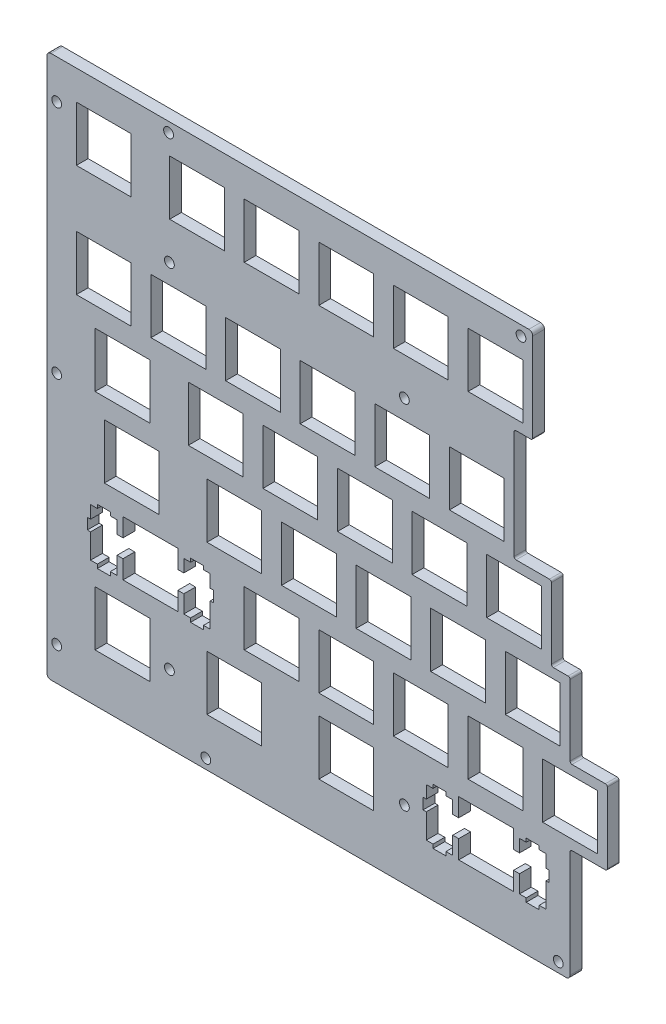
SolidWorks part; units mm, degrees
ref_plane "前视基准面" through (0, 0, 0) normal (0, 0, 1) x (1, 0, 0)
ref_plane "上视基准面" through (0, 0, 0) normal (0, 1, 0) x (1, 0, 0)
ref_plane "右视基准面" through (0, 0, 0) normal (1, 0, 0) x (0, 0, -1)
other "Configuration Table"
sketch "Model" plane through (0, 0, 0) normal (0, 0, 1) x (1, 0, 0)
  line L0 (0.0951, 124.083) -> (119.158, 124.083)
  line L1 (138.208, 124.083) -> (138.208, 0.2577) construction
  line L2 (128.683, 0.2577) -> (0.0951, 0.2577)
  line L3 (0.0951, 0.2577) -> (0.0951, 124.083)
  line L4 (100.251, 16.7831) -> (100.251, 12.0826)
  line L5 (100.251, 12.0826) -> (98.7256, 12.0826)
  line L6 (98.7256, 12.0826) -> (98.7256, 15.3128)
  line L7 (98.7256, 15.3128) -> (97.0001, 15.3128)
  line L8 (97.0001, 15.3128) -> (97.0001, 16.2333)
  line L9 (97.0001, 16.2333) -> (93.701, 16.2333)
  line L10 (93.701, 16.2333) -> (93.701, 15.3128)
  line L11 (93.701, 15.3128) -> (91.9759, 15.3128)
  line L12 (91.9759, 15.3128) -> (91.9759, 12.0826)
  line L13 (91.9759, 12.0826) -> (91.1504, 12.0826)
  line L14 (91.1504, 12.0826) -> (91.1504, 9.2838)
  line L15 (91.1504, 9.2838) -> (91.9759, 9.2838)
  line L16 (91.9759, 9.2838) -> (91.9759, 3.0138)
  line L17 (91.9759, 3.0138) -> (93.701, 3.0138)
  line L18 (93.701, 3.0138) -> (93.701, 2.0326)
  line L19 (93.701, 2.0326) -> (97.0001, 2.0326)
  line L20 (97.0001, 2.0326) -> (97.0001, 3.0138)
  line L21 (97.0001, 3.0138) -> (98.7256, 3.0138)
  line L22 (98.7256, 3.0138) -> (98.7256, 7.4827)
  line L23 (98.7256, 7.4827) -> (100.251, 7.4827)
  line L24 (100.251, 7.4827) -> (100.251, 2.7836)
  line L25 (100.251, 2.7836) -> (114.25, 2.7836)
  line L26 (114.25, 2.7836) -> (114.25, 7.4827)
  line L27 (114.25, 7.4827) -> (115.776, 7.4827)
  line L28 (115.776, 7.4827) -> (115.776, 3.0138)
  line L29 (115.776, 3.0138) -> (117.5, 3.0138)
  line L30 (117.5, 3.0138) -> (117.5, 2.0326)
  line L31 (117.5, 2.0326) -> (120.8, 2.0326)
  line L32 (120.8, 2.0326) -> (120.8, 3.0138)
  line L33 (120.8, 3.0138) -> (122.525, 3.0138)
  line L34 (122.525, 3.0138) -> (122.525, 9.2838)
  line L35 (122.525, 9.2838) -> (123.351, 9.2838)
  line L36 (123.351, 9.2838) -> (123.351, 12.0826)
  line L37 (123.351, 12.0826) -> (122.525, 12.0826)
  line L38 (122.525, 12.0826) -> (122.525, 15.3128)
  line L39 (122.525, 15.3128) -> (120.8, 15.3128)
  line L40 (120.8, 15.3128) -> (120.8, 16.2333)
  line L41 (120.8, 16.2333) -> (117.5, 16.2333)
  line L42 (117.5, 16.2333) -> (117.5, 15.3128)
  line L43 (117.5, 15.3128) -> (115.776, 15.3128)
  line L44 (115.776, 15.3128) -> (115.776, 12.0826)
  line L45 (115.776, 12.0826) -> (114.25, 12.0826)
  line L46 (114.25, 12.0826) -> (114.25, 16.7831)
  line L47 (114.25, 16.7831) -> (100.251, 16.7831)
  line L48 (7.3822, 16.7831) -> (21.3817, 16.7831)
  line L49 (21.3817, 16.7831) -> (21.3817, 2.7836)
  line L50 (21.3817, 2.7836) -> (7.3822, 2.7836)
  line L51 (7.3822, 2.7836) -> (7.3822, 16.7831)
  line L52 (35.9572, 16.7831) -> (49.9565, 16.7831)
  line L53 (49.9565, 16.7831) -> (49.9565, 2.7836)
  line L54 (49.9565, 2.7836) -> (35.9572, 2.7836)
  line L55 (35.9572, 2.7836) -> (35.9572, 16.7831)
  line L56 (64.5322, 16.7831) -> (78.5315, 16.7831)
  line L57 (78.5315, 16.7831) -> (78.5315, 2.7836)
  line L58 (78.5315, 2.7836) -> (64.5322, 2.7836)
  line L59 (64.5322, 2.7836) -> (64.5322, 16.7831)
  line L60 (14.5259, 35.833) -> (14.5259, 31.1326)
  line L61 (14.5259, 31.1326) -> (13.0004, 31.1326)
  line L62 (13.0004, 31.1326) -> (13.0004, 34.3628)
  line L63 (13.0004, 34.3628) -> (11.2751, 34.3628)
  line L64 (11.2751, 34.3628) -> (11.2751, 35.2834)
  line L65 (11.2751, 35.2834) -> (7.9761, 35.2834)
  line L66 (7.9761, 35.2834) -> (7.9761, 34.3628)
  line L67 (7.9761, 34.3628) -> (6.2508, 34.3628)
  line L68 (6.2508, 34.3628) -> (6.2508, 31.1326)
  line L69 (6.2508, 31.1326) -> (5.4253, 31.1326)
  line L70 (5.4253, 31.1326) -> (5.4253, 28.3338)
  line L71 (5.4253, 28.3338) -> (6.2508, 28.3338)
  line L72 (6.2508, 28.3338) -> (6.2508, 22.0638)
  line L73 (6.2508, 22.0638) -> (7.9761, 22.0638)
  line L74 (7.9761, 22.0638) -> (7.9761, 21.0826)
  line L75 (7.9761, 21.0826) -> (11.2751, 21.0826)
  line L76 (11.2751, 21.0826) -> (11.2751, 22.0638)
  line L77 (11.2751, 22.0638) -> (13.0004, 22.0638)
  line L78 (13.0004, 22.0638) -> (13.0004, 26.5327)
  line L79 (13.0004, 26.5327) -> (14.5259, 26.5327)
  line L80 (14.5259, 26.5327) -> (14.5259, 21.8336)
  line L81 (14.5259, 21.8336) -> (28.5254, 21.8336)
  line L82 (28.5254, 21.8336) -> (28.5254, 26.5327)
  line L83 (28.5254, 26.5327) -> (30.0509, 26.5327)
  line L84 (30.0509, 26.5327) -> (30.0509, 22.0638)
  line L85 (30.0509, 22.0638) -> (31.7748, 22.0638)
  line L86 (31.7748, 22.0638) -> (31.7748, 21.0826)
  line L87 (31.7748, 21.0826) -> (35.0752, 21.0826)
  line L88 (35.0752, 21.0826) -> (35.0752, 22.0638)
  line L89 (35.0752, 22.0638) -> (36.8004, 22.0638)
  line L90 (36.8004, 22.0638) -> (36.8004, 28.3338)
  line L91 (36.8004, 28.3338) -> (37.6259, 28.3338)
  line L92 (37.6259, 28.3338) -> (37.6259, 31.1326)
  line L93 (37.6259, 31.1326) -> (36.8004, 31.1326)
  line L94 (36.8004, 31.1326) -> (36.8004, 34.3628)
  line L95 (36.8004, 34.3628) -> (35.0752, 34.3628)
  line L96 (35.0752, 34.3628) -> (35.0752, 35.2834)
  line L97 (35.0752, 35.2834) -> (31.7748, 35.2834)
  line L98 (31.7748, 35.2834) -> (31.7748, 34.3628)
  line L99 (31.7748, 34.3628) -> (30.0509, 34.3628)
  line L100 (30.0509, 34.3628) -> (30.0509, 31.1326)
  line L101 (30.0509, 31.1326) -> (28.5254, 31.1326)
  line L102 (28.5254, 31.1326) -> (28.5254, 35.833)
  line L103 (28.5254, 35.833) -> (14.5259, 35.833)
  line L104 (45.4822, 35.833) -> (59.4815, 35.833)
  line L105 (59.4815, 35.833) -> (59.4815, 21.8336)
  line L106 (59.4815, 21.8336) -> (45.4822, 21.8336)
  line L107 (45.4822, 21.8336) -> (45.4822, 35.833)
  line L108 (64.5322, 35.833) -> (78.5315, 35.833)
  line L109 (78.5315, 35.833) -> (78.5315, 21.8336)
  line L110 (78.5315, 21.8336) -> (64.5322, 21.8336)
  line L111 (64.5322, 21.8336) -> (64.5322, 35.833)
  line L112 (83.5822, 35.833) -> (97.5815, 35.833)
  line L113 (97.5815, 35.833) -> (97.5815, 21.8336)
  line L114 (97.5815, 21.8336) -> (83.5822, 21.8336)
  line L115 (83.5822, 21.8336) -> (83.5822, 35.833)
  line L116 (102.632, 35.833) -> (116.632, 35.833)
  line L117 (116.632, 35.833) -> (116.632, 21.8336)
  line L118 (116.632, 21.8336) -> (102.632, 21.8336)
  line L119 (102.632, 21.8336) -> (102.632, 35.833)
  line L120 (121.682, 35.833) -> (135.682, 35.833)
  line L121 (135.682, 35.833) -> (135.682, 21.8336)
  line L122 (135.682, 21.8336) -> (121.682, 21.8336)
  line L123 (121.682, 21.8336) -> (121.682, 35.833)
  line L124 (9.762, 54.8831) -> (23.7629, 54.8831)
  line L125 (23.7629, 54.8831) -> (23.7629, 40.8838)
  line L126 (23.7629, 40.8838) -> (9.762, 40.8838)
  line L127 (9.762, 40.8838) -> (9.762, 54.8831)
  line L128 (35.9572, 54.8831) -> (49.9565, 54.8831)
  line L129 (49.9565, 54.8831) -> (49.9565, 40.8838)
  line L130 (49.9565, 40.8838) -> (35.9572, 40.8838)
  line L131 (35.9572, 40.8838) -> (35.9572, 54.8831)
  line L132 (55.0072, 54.8831) -> (69.0065, 54.8831)
  line L133 (69.0065, 54.8831) -> (69.0065, 40.8838)
  line L134 (69.0065, 40.8838) -> (55.0072, 40.8838)
  line L135 (55.0072, 40.8838) -> (55.0072, 54.8831)
  line L136 (74.0572, 54.8831) -> (88.0565, 54.8831)
  line L137 (88.0565, 54.8831) -> (88.0565, 40.8838)
  line L138 (88.0565, 40.8838) -> (74.0572, 40.8838)
  line L139 (74.0572, 40.8838) -> (74.0572, 54.8831)
  line L140 (93.1072, 54.8831) -> (107.107, 54.8831)
  line L141 (107.107, 54.8831) -> (107.107, 40.8838)
  line L142 (107.107, 40.8838) -> (93.1072, 40.8838)
  line L143 (93.1072, 40.8838) -> (93.1072, 54.8831)
  line L144 (112.157, 54.8831) -> (126.157, 54.8831)
  line L145 (126.157, 54.8831) -> (126.157, 40.8838)
  line L146 (126.157, 40.8838) -> (112.157, 40.8838)
  line L147 (112.157, 40.8838) -> (112.157, 54.8831)
  line L148 (7.3822, 73.9331) -> (21.3817, 73.9331)
  line L149 (21.3817, 73.9331) -> (21.3817, 59.9338)
  line L150 (21.3817, 59.9338) -> (7.3822, 59.9338)
  line L151 (7.3822, 59.9338) -> (7.3822, 73.9331)
  line L152 (31.1947, 73.9331) -> (45.194, 73.9331)
  line L153 (45.194, 73.9331) -> (45.194, 59.9338)
  line L154 (45.194, 59.9338) -> (31.1947, 59.9338)
  line L155 (31.1947, 59.9338) -> (31.1947, 73.9331)
  line L156 (50.2447, 73.9331) -> (64.244, 73.9331)
  line L157 (64.244, 73.9331) -> (64.244, 59.9338)
  line L158 (64.244, 59.9338) -> (50.2447, 59.9338)
  line L159 (50.2447, 59.9338) -> (50.2447, 73.9331)
  line L160 (69.2947, 73.9331) -> (83.294, 73.9331)
  line L161 (83.294, 73.9331) -> (83.294, 59.9338)
  line L162 (83.294, 59.9338) -> (69.2947, 59.9338)
  line L163 (69.2947, 59.9338) -> (69.2947, 73.9331)
  line L164 (88.3447, 73.9331) -> (102.344, 73.9331)
  line L165 (102.344, 73.9331) -> (102.344, 59.9338)
  line L166 (102.344, 59.9338) -> (88.3447, 59.9338)
  line L167 (88.3447, 59.9338) -> (88.3447, 73.9331)
  line L168 (107.395, 73.9331) -> (121.394, 73.9331)
  line L169 (121.394, 73.9331) -> (121.394, 59.9338)
  line L170 (121.394, 59.9338) -> (107.395, 59.9338)
  line L171 (107.395, 59.9338) -> (107.395, 73.9331)
  line L172 (2.6197, 92.9831) -> (16.6192, 92.9831)
  line L173 (16.6192, 92.9831) -> (16.6192, 78.9838)
  line L174 (16.6192, 78.9838) -> (2.6197, 78.9838)
  line L175 (2.6197, 78.9838) -> (2.6197, 92.9831)
  line L176 (21.6697, 92.9831) -> (35.669, 92.9831)
  line L177 (35.669, 92.9831) -> (35.669, 78.9838)
  line L178 (35.669, 78.9838) -> (21.6697, 78.9838)
  line L179 (21.6697, 78.9838) -> (21.6697, 92.9831)
  line L180 (40.7197, 92.9831) -> (54.719, 92.9831)
  line L181 (54.719, 92.9831) -> (54.719, 78.9838)
  line L182 (54.719, 78.9838) -> (40.7197, 78.9838)
  line L183 (40.7197, 78.9838) -> (40.7197, 92.9831)
  line L184 (59.7697, 92.9831) -> (73.769, 92.9831)
  line L185 (73.769, 92.9831) -> (73.769, 78.9838)
  line L186 (73.769, 78.9838) -> (59.7697, 78.9838)
  line L187 (59.7697, 78.9838) -> (59.7697, 92.9831)
  line L188 (78.8197, 92.9831) -> (92.819, 92.9831)
  line L189 (92.819, 92.9831) -> (92.819, 78.9838)
  line L190 (92.819, 78.9838) -> (78.8197, 78.9838)
  line L191 (78.8197, 78.9838) -> (78.8197, 92.9831)
  line L192 (97.8683, 92.9831) -> (111.869, 92.9831)
  line L193 (111.869, 92.9831) -> (111.869, 78.9838)
  line L194 (111.869, 78.9838) -> (97.8683, 78.9838)
  line L195 (97.8683, 78.9838) -> (97.8683, 92.9831)
  line L196 (2.6197, 121.558) -> (16.6192, 121.558)
  line L197 (16.6192, 121.558) -> (16.6192, 107.559)
  line L198 (16.6192, 107.559) -> (2.6197, 107.559)
  line L199 (2.6197, 107.559) -> (2.6197, 121.558)
  line L200 (26.4322, 121.558) -> (40.4315, 121.558)
  line L201 (40.4315, 121.558) -> (40.4315, 107.559)
  line L202 (40.4315, 107.559) -> (26.4322, 107.559)
  line L203 (26.4322, 107.559) -> (26.4322, 121.558)
  line L204 (45.4822, 121.558) -> (59.4815, 121.558)
  line L205 (59.4815, 121.558) -> (59.4815, 107.559)
  line L206 (59.4815, 107.559) -> (45.4822, 107.559)
  line L207 (45.4822, 107.559) -> (45.4822, 121.558)
  line L208 (64.5322, 121.558) -> (78.5315, 121.558)
  line L209 (78.5315, 121.558) -> (78.5315, 107.559)
  line L210 (78.5315, 107.559) -> (64.5322, 107.559)
  line L211 (64.5322, 107.559) -> (64.5322, 121.558)
  line L212 (83.5822, 121.558) -> (97.5815, 121.558)
  line L213 (97.5815, 121.558) -> (97.5815, 107.559)
  line L214 (97.5815, 107.559) -> (83.5822, 107.559)
  line L215 (83.5822, 107.559) -> (83.5822, 121.558)
  line L216 (102.632, 121.558) -> (116.632, 121.558)
  line L217 (116.632, 121.558) -> (116.632, 107.559)
  line L218 (116.632, 107.559) -> (102.632, 107.559)
  line L219 (102.632, 107.559) -> (102.632, 121.558)
  line L233 (114.395, 76.453) -> (114.395, 105.033)
  line L234 (128.683, 19.303) -> (128.683, 0.2577)
  line L235 (114.395, 105.033) -> (119.158, 105.033)
  line L236 (119.158, 105.033) -> (119.158, 124.083)
  line L237 (114.395, 76.453) -> (123.92, 76.453)
  line L238 (123.92, 76.453) -> (123.92, 57.403)
  line L239 (123.92, 57.403) -> (128.683, 57.403)
  line L240 (128.683, 57.403) -> (128.683, 38.353)
  line L241 (128.683, 38.353) -> (138.208, 38.353)
  line L242 (138.208, 38.353) -> (138.208, 19.303)
  line L243 (138.208, 19.303) -> (128.683, 19.303)
  dimension "D1" = 19.05
  dimension "D2" = 4.763
  dimension "D3" = 28.58
  dimension "D4" = 9.525
extrude "凸台-拉伸1" add sketch "Model" along normal blind 3
sketch "草图5" plane through (0, 0.2577, 0) normal (0, -1, 0) x (1, 0, 0)
  line L4 (0.0951, 0) -> (128.683, 0)
  line L5 (128.683, 0) -> (128.683, 3)
  line L6 (128.683, 3) -> (0.0951, 3)
  line L7 (0.0951, 3) -> (0.0951, 0)
  line L8 (0.0951, 0) -> (128.683, 0)
  line L9 (128.683, 0) -> (128.683, 3)
  line L10 (128.683, 3) -> (0.0951, 3)
  line L11 (0.0951, 3) -> (0.0951, 0)
  dimension "D1" = 0
extrude "凸台-拉伸3" add sketch "草图5" along normal blind 4.76
sketch "草图2" plane through (0, 0, 3) normal (0, 0, 1) x (1, 0, 0)
  line L11 (119.158, 124.083) -> (0.0951, 124.083) construction
  line L12 (0.0951, 124.083) -> (0.0951, -4.5023) construction
  line L13 (128.683, -4.5023) -> (0.0951, -4.5023) construction
  line L14 (119.158, 124.083) -> (0.0951, 124.083)
  line L15 (0.0951, 124.083) -> (0.0951, -4.5023)
  line L16 (128.683, -4.5023) -> (0.0951, -4.5023)
  line L17 (119.158, 129.083) -> (-4.9049, 129.083)
  line L18 (-4.9049, 129.083) -> (-4.9049, -9.5023)
  line L19 (128.683, -9.5023) -> (-4.9049, -9.5023)
  line L20 (119.158, 124.083) -> (119.158, 129.083)
  line L21 (128.683, -9.5023) -> (128.683, -4.5023)
  dimension "D1" = 5
extrude "凸台-拉伸2" add sketch "草图2" against normal blind 3
sketch "草图3" plane through (0, 0, 3) normal (0, 0, 1) x (1, 0, 0)
  line L0 (119.158, 105.033) -> (119.158, 129.083) construction
  line L2 (128.683, -9.5023) -> (128.683, 19.303) construction
  line L4 (-4.9049, -9.5023) -> (128.683, -9.5023) construction
  line L5 (119.158, 129.083) -> (-4.9049, 129.083) construction
  circle A0 centre (125.683, -7.0023) radius 1.25
  circle A1 centre (116.158, 126.583) radius 1.25
  dimension "D1" = 2.5
  dimension "D2" = 3
  dimension "D3" = 2.5
  dimension "D4" = 3
  dimension "D5" = 2.5
extrude "切除-拉伸1" cut sketch "草图3" against normal blind 3
pattern_linear "阵列(线性)1" count 2 spacing 90 along (-1, 0, 0) of "切除-拉伸1"
sketch "草图4" plane through (0, 0, 3) normal (0, 0, 1) x (1, 0, 0)
  line L2 (-4.9049, 129.083) -> (-4.9049, -9.5023) construction
  line L3 (119.158, 129.083) -> (-4.9049, 129.083) construction
  circle A0 centre (-2.4049, 119.083) radius 1.25
  dimension "D1" = 2.5
  dimension "D2" = 2.5
  dimension "D3" = 10
extrude "切除-拉伸2" cut sketch "草图4" against normal blind 3
pattern_linear "阵列(线性)2" count 3 spacing 60 along (0, -1, 0) of "切除-拉伸2"
fillet "圆角1" radius 1 4 edges at (-4.9049, -9.5023, 1.5) (128.683, -9.5023, 1.5) (119.158, 129.083, 1.5) (-4.9049, 129.083, 1.5)
fillet "圆角2" radius 0.5 10 edges at (119.158, 105.033, 1.5) (114.395, 105.033, 1.5) (123.92, 76.453, 1.5) (114.395, 76.453, 1.5) (128.683, 57.403, 1.5) (123.92, 57.403, 1.5) (138.208, 38.353, 1.5) (128.683, 38.353, 1.5) (138.208, 19.303, 1.5) (128.683, 19.303, 1.5)
sketch "草图6" plane through (0, 0, 3) normal (0, 0, 1) x (1, 0, 0)
  line L0 (54.719, 92.9831) -> (40.7197, 92.9831) construction
  line L1 (26.3817, 97.9831) -> (86.3817, 97.9831) construction
  line L2 (26.3817, 97.9831) -> (26.3817, 7.9831) construction
  line L3 (26.3817, 7.9831) -> (86.3817, 7.9831) construction
  line L4 (86.3817, 97.9831) -> (86.3817, 7.9831) construction
  line L5 (21.3817, 2.7836) -> (21.3817, 16.7831) construction
  circle A3 centre (26.3817, 7.9831) radius 1.25
  circle A4 centre (86.3817, 7.9831) radius 1.25
  circle A5 centre (86.3817, 97.9831) radius 1.25
  circle A6 centre (26.3817, 97.9831) radius 1.25
  dimension "D1" = 60
  dimension "D5" = 2.5
  dimension "D2" = 90
  dimension "D3" = 5
  dimension "D4" = 5
extrude "切除-拉伸3" cut sketch "草图6" against normal blind 10
